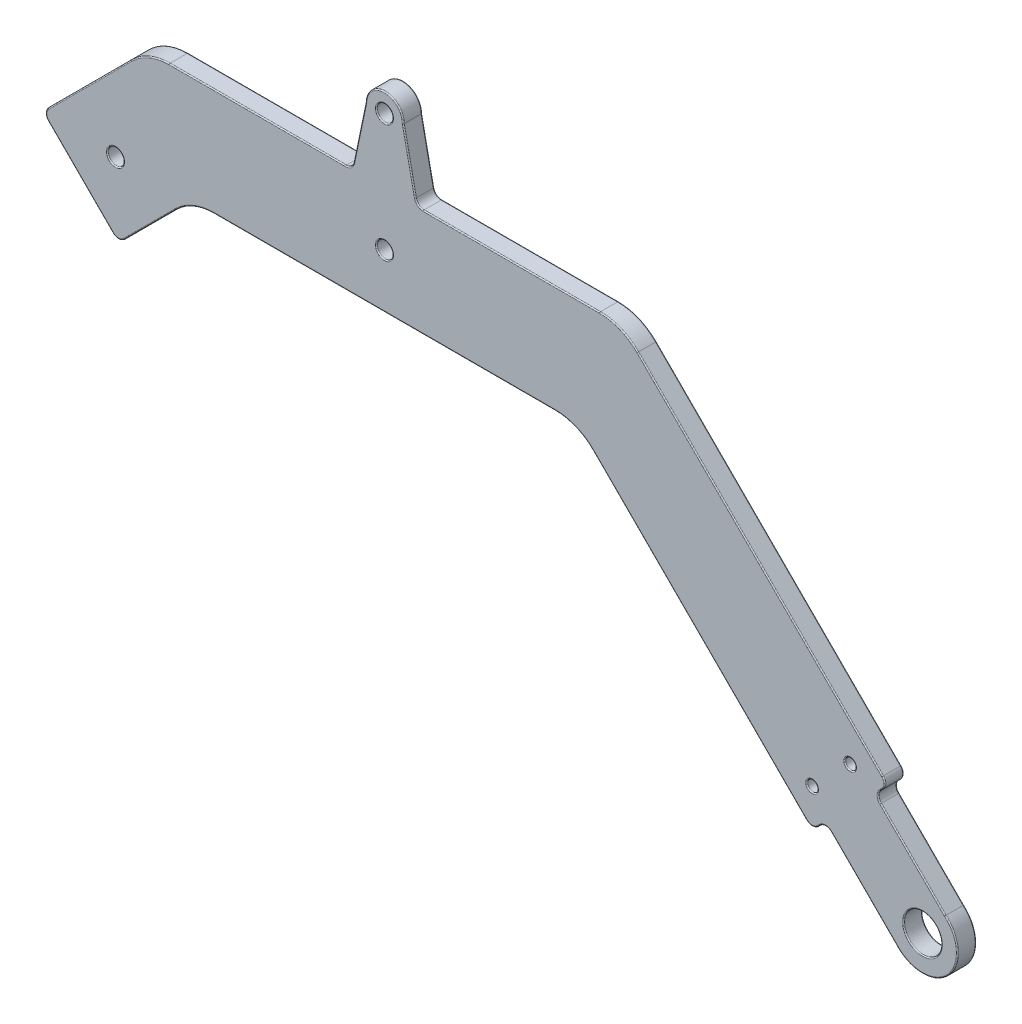
SolidWorks part; units mm, degrees
ref_plane "Front Plane" through (0, 0, 0) normal (0, 0, 1) x (1, 0, 0)
ref_plane "Top Plane" through (0, 0, 0) normal (0, 1, 0) x (1, 0, 0)
ref_plane "Right Plane" through (0, 0, 0) normal (1, 0, 0) x (0, 0, -1)
sketch "Sketch1" plane through (0, 0, 0) normal (0, 0, 1) x (1, 0, 0)
  line L0 (-100, 0) -> (100, 0) construction
  line L1 (-100, 0) -> (0, 100) construction
  line L2 (0, 100) -> (100, 0) construction
  line L3 (0, 0) -> (-50, 50) construction
  line L4 (-40, 60) -> (40, 60) construction
  line L5 (0, 100) -> (0, 60) construction
  circle A0 centre (-100, 0) radius 20
  circle A1 centre (0, 0) radius 20
  circle A2 centre (100, 0) radius 20
  point P3 (0, 0)
  dimension "D5" = 40
  dimension "D1" = 200
  dimension "D2" = 90
  dimension "D3" = 80
  dimension "D4" = 90
sketch "Sketch2" plane through (0, 0, 0) normal (0, 0, 1) x (1, 0, 0)
  line L0 (-56.5165, 43.4835) -> (-40, 60) construction
  line L1 (-100, 0) -> (0, 100) construction
  line L2 (-40, 60) -> (40, 60) construction
  line L3 (40, 60) -> (86.565, 13.435) construction
  line L4 (0, 100) -> (100, 0) construction
  line L5 (-49.4454, 36.4124) -> (-35.8579, 50)
  line L6 (-35.8579, 50) -> (35.8579, 50)
  line L7 (35.8579, 50) -> (79.4939, 6.364)
  line L8 (-63.5876, 50.5546) -> (-44.1421, 70)
  line L9 (-44.1421, 70) -> (44.1421, 70)
  line L10 (44.1421, 70) -> (93.636, 20.5061)
  line L11 (-63.5876, 50.5546) -> (-49.4454, 36.4124)
  line L12 (79.4939, 6.364) -> (93.636, 20.5061)
  line L13 (81.9812, 8.8513) -> (95.0783, -4.2458)
  line L14 (91.1473, 18.0173) -> (104.225, 4.9396)
  line L15 (75.9584, 9.8995) -> (90.1005, 24.0416) construction
  line L16 (0, 100) -> (0, 60) construction
  line L17 (-6, 70) -> (-3.5, 82)
  line L18 (6, 70) -> (3.5, 82)
  circle A0 centre (100, 0) radius 10 construction
  circle A1 centre (100, 0) radius 3.5
  arc A2 (95.0783, -4.2458) -> (104.225, 4.9396) centre (100, 0) ccw
  circle A3 centre (100, 0) radius 0.5
  circle A4 centre (79.4939, 13.435) radius 1
  circle A5 centre (100, 0) radius 6.5 construction
  circle A6 centre (86.565, 20.5061) radius 1
  circle A7 centre (0, 60) radius 1.5
  circle A8 centre (0, 82) radius 1.5
  arc A11 (3.5, 82) -> (-3.5, 82) centre (0, 82) ccw
  circle A12 centre (-50, 50) radius 1.5
  circle A13 centre (0, 82) radius 3.5 construction
  point P30 (106.5, 0)
  point P50 (3.5, 82)
  dimension "D4" = 7
  dimension "D7" = 20
  dimension "D10" = 2
  dimension "D11" = 5
  dimension "D12" = 5
  dimension "D13" = 3
  dimension "D14" = 12
  dimension "D18" = 3
  dimension "D3" = 27.5
  dimension "D8" = 19
  dimension "D9" = 5
  dimension "D16" = 6
  dimension "D17" = 6
  dimension "D1" = 10
  dimension "D2" = 10
  dimension "D5" = 3
  dimension "D6" = 3
  dimension "D15" = 2
sketch "Sketch3" plane through (0, 0, 0) normal (0, 0, 1) x (1, 0, 0)
  line L0 (-86.565, 13.435) -> (-50, 50) construction
  line L1 (-100, 0) -> (0, 100) construction
  line L2 (-50, 50) -> (-13.435, 13.435) construction
  line L3 (0, 0) -> (-50, 50) construction
  line L4 (-79.4939, 6.364) -> (-50, 35.8579)
  line L5 (-50, 35.8579) -> (-20.5061, 6.364)
  line L6 (-93.636, 20.5061) -> (-50, 64.1421)
  line L7 (-50, 64.1421) -> (-6.364, 20.5061)
  line L8 (-94.9578, 19.1843) -> (-50, 64.1421) construction
  line L9 (-80.8157, 5.0422) -> (-50, 35.8579) construction
  line L10 (-93.636, 20.5061) -> (-79.4939, 6.364)
  line L11 (-20.5061, 6.364) -> (-6.364, 20.5061)
  line L12 (-87.8868, 12.1132) -> (-50, 50) construction
  line L13 (-91.121, 17.991) -> (-103.9494, 5.1626)
  line L14 (-81.9688, 8.8389) -> (-95.425, -4.6173)
  line L15 (-17.8509, 9.0191) -> (-4.6576, -4.534)
  line L16 (-8.8388, 18.0312) -> (4.5962, 4.5962)
  line L17 (-90.1005, 24.0416) -> (-75.9584, 9.8995) construction
  line L18 (-24.0416, 9.8995) -> (-9.8995, 24.0416) construction
  circle A0 centre (-100, 0) radius 10 construction
  circle A1 centre (-100, 0) radius 3.5
  circle A2 centre (0, 0) radius 10 construction
  circle A3 centre (0, 0) radius 3.5
  arc A4 (-4.6576, -4.534) -> (4.5962, 4.5962) centre (0, 0) ccw
  circle A5 centre (-100, 0) radius 6.5
  circle A6 centre (0, 0) radius 20 construction
  circle A7 centre (-86.565, 20.5061) radius 1
  circle A8 centre (0, 0) radius 6.5 construction
  circle A9 centre (-79.4939, 13.435) radius 1
  circle A10 centre (-20.5061, 13.435) radius 1
  circle A11 centre (-13.435, 20.5061) radius 1
  point P39 (6.5, 0)
  dimension "D1" = 20
  dimension "D2" = 7
  dimension "D8" = 2
  dimension "D6" = 19
  dimension "D7" = 19
  dimension "D9" = 5
  dimension "D10" = 5
  dimension "D11" = 5
  dimension "D12" = 5
  dimension "D13" = 5
  dimension "D14" = 5
  dimension "D3" = 3
  dimension "D4" = 10
  dimension "D5" = 10
sketch "Sketch4" plane through (0, 0, 0) normal (0, 0, 1) x (1, 0, 0)
  line L1 (57.5, 90.5) -> (57.5, 80.5)
  line L2 (57.5, 80.5) -> (44.1421, 70)
  line L3 (44.1421, 70) -> (-44.1421, 70)
  line L4 (-44.1421, 70) -> (-57.5, 80.5)
  line L5 (-57.5, 80.5) -> (-57.5, 90.5)
  line L6 (-57.5, 90.5) -> (57.5, 90.5)
  line L7 (-4, 60) -> (-4, 70)
  line L8 (4, 60) -> (4, 70)
  line L9 (-22.5, 82) -> (22.5, 82) construction
  line L10 (-22.5, 86.5) -> (22.5, 86.5)
  line L11 (-22.5, 77.5) -> (22.5, 77.5)
  circle A0 centre (0, 60) radius 1.5 construction
  circle A1 centre (0, 60) radius 1.5
  arc A2 (-4, 60) -> (4, 60) centre (0, 60) ccw
  arc A3 (-22.5, 86.5) -> (-22.5, 77.5) centre (-22.5, 82) ccw
  circle A4 centre (0, 60) radius 4 construction
  arc A5 (22.5, 77.5) -> (22.5, 86.5) centre (22.5, 82) ccw
  point P3 (0, 111.8578)
  point P19 (4, 60)
  point P22 (0, 82)
  point P27 (0, 0)
  point P28 (0, 0)
  point P29 (0, 0)
  dimension "D5" = 9
  dimension "D1" = 115
  dimension "D2" = 10
  dimension "D4" = 45
  dimension "D6" = 4
  dimension "D3" = 2.5
sketch "Sketch5" plane through (0, 0, 0) normal (0, 0, 1) x (1, 0, 0)
  line L0 (91.1473, 18.0173) -> (104.225, 4.9396) construction
  line L1 (81.9812, 8.8513) -> (95.0783, -4.2458) construction
  line L2 (6, 70) -> (3.5, 82) construction
  line L3 (-6, 70) -> (-3.5, 82) construction
  line L4 (91.1473, 18.0173) -> (104.225, 4.9396)
  line L5 (81.9812, 8.8513) -> (95.0783, -4.2458)
  line L6 (6, 70) -> (3.5, 82)
  line L7 (-6, 70) -> (-3.5, 82)
  line L8 (93.636, 20.5061) -> (44.1421, 70)
  line L9 (79.4939, 6.364) -> (93.636, 20.5061)
  line L10 (35.8579, 50) -> (79.4939, 6.364)
  line L11 (-35.8579, 50) -> (35.8579, 50)
  line L12 (-49.4454, 36.4124) -> (-35.8579, 50)
  line L13 (-63.5876, 50.5546) -> (-49.4454, 36.4124)
  line L14 (-44.1421, 70) -> (-63.5876, 50.5546)
  line L15 (44.1421, 70) -> (-44.1421, 70)
  line L16 (93.636, 20.5061) -> (44.1421, 70)
  line L17 (79.4939, 6.364) -> (81.9812, 8.8513)
  line L18 (35.8579, 50) -> (79.4939, 6.364)
  line L19 (-35.8579, 50) -> (35.8579, 50)
  line L20 (-49.4454, 36.4124) -> (-35.8579, 50)
  line L21 (-63.5876, 50.5546) -> (-49.4454, 36.4124)
  line L22 (-44.1421, 70) -> (-63.5876, 50.5546)
  line L23 (44.1421, 70) -> (6, 70)
  line L24 (-6, 70) -> (-44.1421, 70)
  line L25 (91.1473, 18.0173) -> (93.636, 20.5061)
  arc A0 (95.0783, -4.2458) -> (104.225, 4.9396) centre (100, 0) ccw construction
  circle A1 centre (100, 0) radius 0.5
  circle A2 centre (100, 0) radius 0.5
  circle A3 centre (100, 0) radius 3.5
  circle A4 centre (100, 0) radius 3.5
  circle A5 centre (0, 82) radius 1.5
  circle A6 centre (0, 82) radius 1.5
  circle A7 centre (0, 60) radius 1.5
  circle A8 centre (0, 60) radius 1.5
  circle A9 centre (86.565, 20.5061) radius 1
  circle A10 centre (86.565, 20.5061) radius 1
  circle A11 centre (79.4939, 13.435) radius 1
  circle A12 centre (79.4939, 13.435) radius 1
  circle A13 centre (-50, 50) radius 1.5
  circle A14 centre (-50, 50) radius 1.5
  arc A15 (3.5, 82) -> (-3.5, 82) centre (0, 82) ccw construction
  arc A16 (95.0783, -4.2458) -> (104.225, 4.9396) centre (100, 0) ccw
  arc A17 (3.5, 82) -> (-3.5, 82) centre (0, 82) ccw
  dimension "D1" = 0
  dimension "D2" = 0
  dimension "D3" = 0
  dimension "D4" = 0
  dimension "D5" = 0
  dimension "D6" = 0
  dimension "D7" = 0
  dimension "D8" = 0
extrude "Boss-Extrude1" add sketch "Sketch5" along normal blind 3.5 contours L6 A17 L7 L24 L22 L21 L20 L19 L18 L17 L5 A16 L4 L25 L16 L23 A4 A6 A8 A10 A12 A14 region at (94.4374, 5.5613, 0) region at (18.0255, 50.1428, 0) region at (0, 76.3299, 0)
fillet "Fillet1" radius 10 4 edges at (35.8579, 50, 1.75) (-35.8579, 50, 1.75) (44.1421, 70, 1.75) (-44.1421, 70, 1.75)
fillet "Fillet2" radius 1.5 8 edges at (-49.4454, 36.4124, 1.75) (-63.5876, 50.5546, 1.75) (6, 70, 1.75) (-6, 70, 1.75) (79.4939, 6.364, 1.75) (81.9812, 8.8513, 1.75) (91.1473, 18.0173, 1.75) (93.636, 20.5061, 1.75)
fillet "Fillet3" radius 0.2 72 edges at (103.5, 0, 0) (1.5, 82, 0) (1.5, 60, 0) (87.565, 20.5061, 0) (80.4939, 13.435, 0) (-48.5, 50, 0) (4.6256, 76.597, 0) (0, 85.5, 0) (-4.6256, 76.597, 0) (-23.6099, 70, 0) (-54.799, 59.3431, 0) (-56.5165, 43.4835, 0) (-43.5858, 42.2721, 0) (0, 50, 0) (58.61, 27.2478, 0) (80.7376, 7.6076, 0) (89.0601, 1.7724, 0) (104.6059, -4.5865, 0) (98.2165, 10.9481, 0) (92.3916, 19.2617, 0) (23.6099, 70, 0) (103.5, 0, 3.5) (1.5, 82, 3.5) (1.5, 60, 3.5) (87.565, 20.5061, 3.5) (80.4939, 13.435, 3.5) (-48.5, 50, 3.5) (4.6256, 76.597, 3.5) (0, 85.5, 3.5) (-4.6256, 76.597, 3.5) (-23.6099, 70, 3.5) (-54.799, 59.3431, 3.5) (-56.5165, 43.4835, 3.5) (-43.5858, 42.2721, 3.5) (0, 50, 3.5) (58.61, 27.2478, 3.5) (80.7376, 7.6076, 3.5) (89.0601, 1.7724, 3.5) (104.6059, -4.5865, 3.5) (98.2165, 10.9481, 3.5) (92.3916, 19.2617, 3.5) (69.8232, 44.3189, 3.5) (23.6099, 70, 3.5) (104.225, 4.9396, 1.75) (95.0783, -4.2458, 1.75) (-3.5, 82, 1.75) (3.5, 82, 1.75) (-43.8268, 69.2388, 0) (43.8268, 69.2388, 0) (-43.8268, 69.2388, 3.5) (43.8268, 69.2388, 3.5) (35.5426, 49.2388, 0) (35.5426, 49.2388, 3.5) (-35.5426, 49.2388, 0) (-35.5426, 49.2388, 3.5) (93.0147, 20.5061, 0) (79.4939, 6.9853, 0) (-62.9663, 50.5546, 0) (-49.4454, 37.0337, 0) (93.0147, 20.5061, 3.5) (79.4939, 6.9853, 3.5) (-62.9663, 50.5546, 3.5) (-49.4454, 37.0337, 3.5) (6.2734, 70.3362, 0) (6.2734, 70.3362, 3.5) (-6.2734, 70.3362, 0) (-6.2734, 70.3362, 3.5) (81.9812, 8.23, 0) (81.9812, 8.23, 3.5) (91.7686, 18.0173, 0) (91.7686, 18.0173, 3.5) (69.8232, 44.3189, 0)
